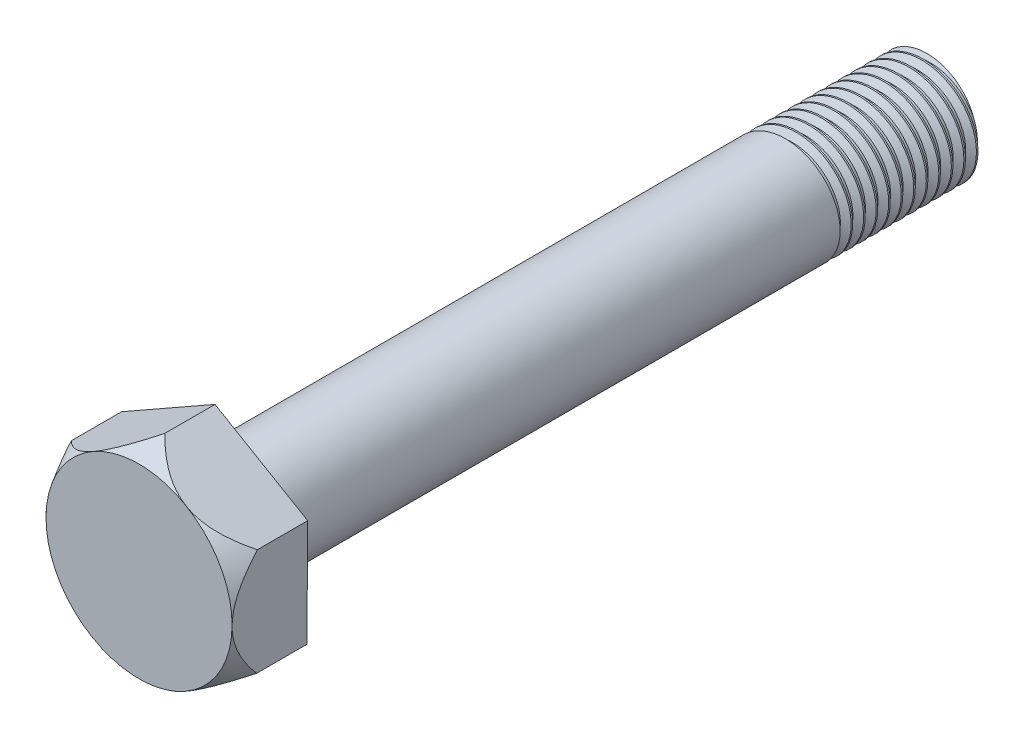
SolidWorks part; units mm, degrees
ref_plane "Front Plane" through (0, 0, 0) normal (0, 0, 1) x (1, 0, 0)
ref_plane "Top Plane" through (0, 0, 0) normal (0, 1, 0) x (1, 0, 0)
ref_plane "Right Plane" through (0, 0, 0) normal (1, 0, 0) x (0, 0, -1)
sketch "Sketch1" plane through (0, 0, 0) normal (0, 0, 1) x (1, 0, 0)
  line L1 (26.0871, 14.8158) -> (0.2127, 30)
  line L2 (0.2127, 30) -> (-25.8744, 15.1842)
  line L3 (-25.8744, 15.1842) -> (-26.0871, -14.8158)
  line L4 (-26.0871, -14.8158) -> (-0.2127, -30)
  line L5 (-0.2127, -30) -> (25.8744, -15.1842)
  line L6 (25.8744, -15.1842) -> (26.0871, 14.8158)
  circle A0 centre (0, 0) radius 25.9814 construction
  dimension "D1" = 60
extrude "Boss-Extrude1" add sketch "Sketch1" along normal blind 21
sketch "Sketch2" plane through (0, 0, 21) normal (0, 0, 1) x (1, 0, 0)
  circle A0 centre (0, 0) radius 25.9814
extrude "Cut-Extrude1" cut sketch "Sketch2" against normal blind 21 draft 30 flip side to cut
sketch "Sketch3" plane through (0, 0, 0) normal (0, 0, -1) x (-1, 0, 0)
  circle A0 centre (0, 0) radius 15
  dimension "D1" = 30
extrude "Boss-Extrude3" add sketch "Sketch3" along normal blind 200
thread "Thread1" pitch 3.5 method cut profile "Thread Profile3" start angle 0, offset 158, length 0, pitch 3.5, diameter 30
ref_plane "Plane3" through (-15, 0, -158) normal (0, -1, 0) x (-1, 0, 0)
sketch "Thread Profile3" plane through (-15, 0, -158) normal (0, -1, 0) x (-1, 0, 0)
  line L0 (0, 0) -> (0, 3.5) construction
  line L11 (0, 0) -> (0, 3.0625)
  line L12 (0, 3.0625) -> (-1.8944, 1.9687)
  line L13 (-1.8944, 1.9687) -> (-1.8944, 1.0937)
  line L15 (-1.8944, 1.0937) -> (0, 0)
  line L17 (-1.8944, 1.5312) -> (0, 1.5312) construction
  point P2 (0, 0)
  dimension "Pitch" = 3.5
  dimension "Profile_Angle" = 60
  dimension "Profile_Land" = 0.875
  dimension "Profile_Height" = 1.8944
